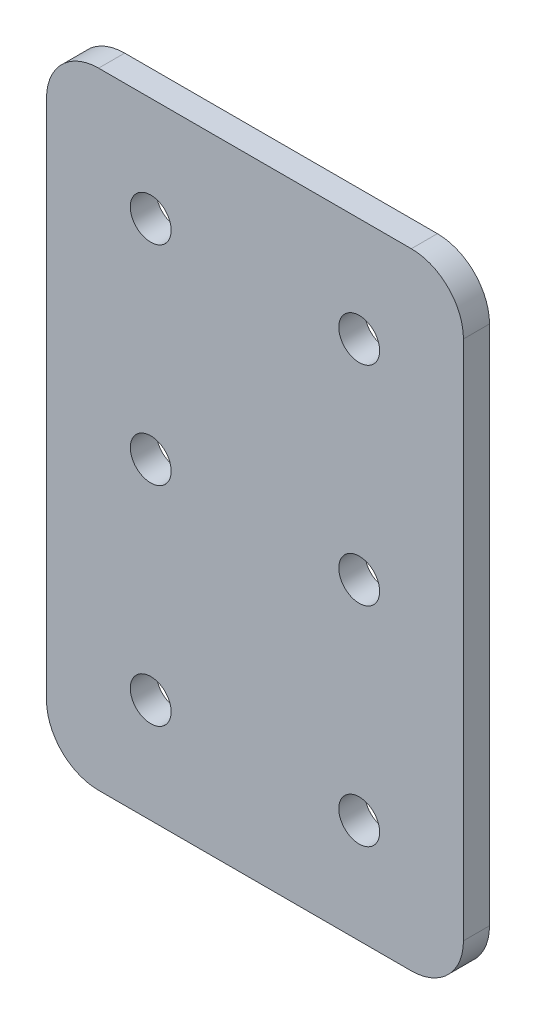
SolidWorks part; units mm, degrees
material "6061-T6 (SS)"
ref_plane "Front Plane" through (0, 0, 0) normal (0, 0, 1) x (1, 0, 0)
ref_plane "Top Plane" through (0, 0, 0) normal (0, 1, 0) x (1, 0, 0)
ref_plane "Right Plane" through (0, 0, 0) normal (1, 0, 0) x (0, 0, -1)
sketch "Sketch2" plane through (0, 0, 0) normal (0, 0, 1) x (1, 0, 0)
  line L1 (0, 0) -> (50.8, 0)
  line L2 (0, 0) -> (0, 76.2)
  line L3 (0, 76.2) -> (50.8, 76.2)
  line L4 (50.8, 0) -> (50.8, 76.2)
  dimension "D1" = 50.8
  dimension "D2" = 76.2
extrude "Boss-Extrude1" add sketch "Sketch2" against normal blind 3.175
sketch "Sketch3" plane through (0, 0, 0) normal (0, 0, 1) x (1, 0, 0)
  line L0 (50.8, 76.2) -> (0, 76.2) construction
  line L1 (0, 76.2) -> (0, 0) construction
  circle A0 centre (12.7, 63.5) radius 2.4892
  circle A17 centre (38.1, 63.5) radius 2.4892
  circle A41 centre (12.7, 38.1) radius 2.4892
  circle A42 centre (12.7, 12.7) radius 2.4892
  circle A43 centre (38.1, 38.1) radius 2.4892
  circle A44 centre (38.1, 12.7) radius 2.4892
  dimension "D1" = 4.9784
  dimension "D2" = 12.7
  dimension "D3" = 12.7
  dimension "D4" = 3
  dimension "D5" = 2
extrude "Cut-Extrude1" cut sketch "Sketch3" against normal through all
fillet "Fillet1" radius 6.35 4 edges at (0, 0, -1.5875) (50.8, 0, -1.5875) (50.8, 76.2, -1.5875) (0, 76.2, -1.5875)
